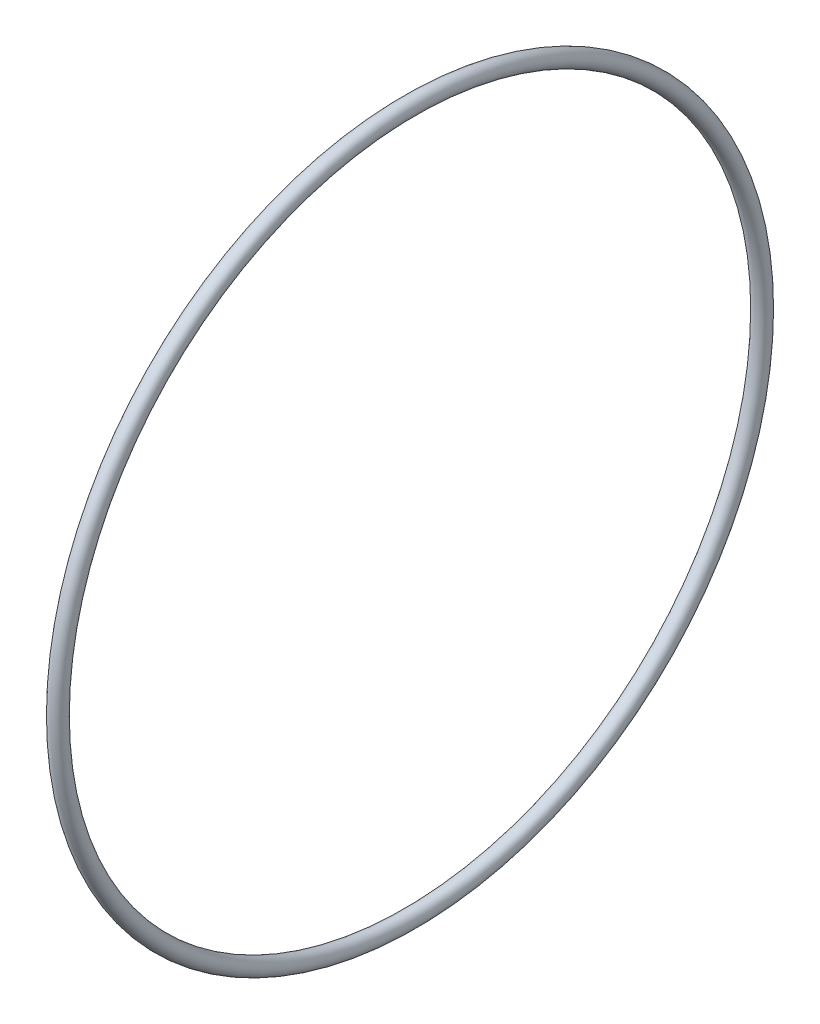
SolidWorks part; units mm, degrees
material "O-Ring (NBR)"
ref_plane "Front Plane" through (0, 0, 0) normal (0, 0, 1) x (1, 0, 0)
ref_plane "Top Plane" through (0, 0, 0) normal (0, 1, 0) x (1, 0, 0)
ref_plane "Right Plane" through (0, 0, 0) normal (1, 0, 0) x (0, 0, -1)
sketch "Sketch3" plane through (0, 0, 0) normal (0, 0, -1) x (-1, 0, 0)
  line L0 (0, 0) -> (5.9943, 0) construction
  circle A0 centre (0, 43.5) radius 1
  dimension "D1" = 85
  dimension "D2" = 2
revolve "Revolve1" add sketch "Sketch3" angle 360 about L0
ref_axis "Axis1" through (-1.1, 0, 0) along (1, 0, 0)
sketch "Sketch1" plane through (0, 0, 0) normal (1, 0, 0) x (0, 0, -1)
  line L0 (-8.772, -54.25) -> (8.772, -54.25)
  line L1 (8.772, 54.25) -> (-8.772, 54.25)
  line L2 (-8.772, -53) -> (8.772, -53) construction
  line L3 (8.772, 53) -> (-8.772, 53) construction
  arc A0 (8.772, -54.25) -> (11.5054, -52.7581) centre (8.772, -51) ccw
  arc A1 (11.5054, 52.7581) -> (8.772, 54.25) centre (8.772, 51) ccw
  arc A2 (-8.772, 54.25) -> (-11.5054, 52.7581) centre (-8.772, 51) ccw
  arc A3 (-11.5054, -52.7581) -> (-8.772, -54.25) centre (-8.772, -51) ccw
  arc A4 (-10.4541, -52.0819) -> (-8.772, -53) centre (-8.772, -51) ccw construction
  arc A5 (8.772, -53) -> (10.4541, -52.0819) centre (8.772, -51) ccw construction
  arc A6 (10.4541, 52.0819) -> (8.772, 53) centre (8.772, 51) ccw construction
  arc A7 (-8.772, 53) -> (-10.4541, 52.0819) centre (-8.772, 51) ccw construction
  spline S0 degree 3 poles (-10.4541, 52.0819) (-16.6114, 42.5088) (-22.7687, 32.9357) (-29.3513, 22.7014) (-29.7886, 22.0215) (-30.4772, 20.9509) (-30.7216, 20.5384) (-31.1954, 19.6712) (-31.4169, 19.2292) (-32.0331, 17.8809) (-32.3797, 16.9524) (-32.9371, 15.0555) (-33.1478, 14.0871) (-33.3589, 12.6197) (-33.4118, 12.1282) (-33.4823, 11.1425) (-33.5, 10.6633) (-33.5, 9.7432) (-33.5, 9.3081) (-33.5, 2.9617) (-33.5, -2.9617) (-33.5, -9.3081) (-33.5, -9.7432) (-33.5, -10.6633) (-33.4823, -11.1425) (-33.4118, -12.1282) (-33.3589, -12.6197) (-33.1478, -14.0871) (-32.9371, -15.0555) (-32.3797, -16.9524) (-32.0331, -17.8809) (-31.4169, -19.2292) (-31.1954, -19.6712) (-30.7216, -20.5384) (-30.4772, -20.9509) (-29.7886, -22.0215) (-29.3513, -22.7014) (-22.7687, -32.9357) (-16.6114, -42.5088) (-10.4541, -52.0819) knots 0.542776 0.542776 0.542776 0.542776 0.662235 0.662235 0.670486 0.670486 0.675984 0.675984 0.681483 0.681483 0.692481 0.692481 0.703479 0.703479 0.708978 0.708978 0.714476 0.714476 0.718917 0.718917 0.781083 0.781083 0.785524 0.785524 0.791022 0.791022 0.796521 0.796521 0.807519 0.807519 0.818517 0.818517 0.824016 0.824016 0.829514 0.829514 0.837765 0.837765 0.957224 0.957224 0.957224 0.957224 construction
  spline S1 degree 3 poles (10.4541, -52.0819) (16.6114, -42.5088) (22.7687, -32.9357) (29.3513, -22.7014) (29.7886, -22.0215) (30.4772, -20.9509) (30.7216, -20.5384) (31.1954, -19.6712) (31.4169, -19.2292) (32.0331, -17.8809) (32.3797, -16.9524) (32.9371, -15.0555) (33.1478, -14.0871) (33.3589, -12.6197) (33.4118, -12.1282) (33.4823, -11.1425) (33.5, -10.6633) (33.5, -9.7432) (33.5, -9.3081) (33.5, -2.9617) (33.5, 2.9617) (33.5, 9.3081) (33.5, 9.7432) (33.5, 10.6633) (33.4823, 11.1425) (33.4118, 12.1282) (33.3589, 12.6197) (33.1478, 14.0871) (32.9371, 15.0555) (32.3797, 16.9524) (32.0331, 17.8809) (31.4169, 19.2292) (31.1954, 19.6712) (30.7216, 20.5384) (30.4772, 20.9509) (29.7886, 22.0215) (29.3513, 22.7014) (22.7687, 32.9357) (16.6114, 42.5088) (10.4541, 52.0819) knots 0.042776 0.042776 0.042776 0.042776 0.162235 0.162235 0.170486 0.170486 0.175984 0.175984 0.181483 0.181483 0.192481 0.192481 0.203479 0.203479 0.208978 0.208978 0.214476 0.214476 0.218917 0.218917 0.281083 0.281083 0.285524 0.285524 0.291022 0.291022 0.296521 0.296521 0.307519 0.307519 0.318517 0.318517 0.324016 0.324016 0.329514 0.329514 0.337765 0.337765 0.457224 0.457224 0.457224 0.457224 construction
  spline S2 degree 3 poles (11.5054, -52.7581) (14.1756, -48.6065) (18.181, -42.3794) (22.854, -35.1136) (25.5242, -30.9628) (27.5271, -27.8466) (29.1952, -25.2599) (30.532, -23.1677) (31.8913, -21.1106) (33.2794, -18.3537) (34.3594, -14.7921) (34.7601, -11.7315) (34.7481, -9.257) (34.7511, -6.7863) (34.7496, -3.7024) (34.7502, 0) (34.7496, 3.7024) (34.7511, 6.7863) (34.7481, 9.257) (34.7601, 11.7315) (34.3594, 14.7921) (33.2794, 18.3537) (31.8913, 21.1106) (30.532, 23.1677) (29.1952, 25.2599) (27.5271, 27.8466) (25.5242, 30.9628) (22.854, 35.1136) (18.181, 42.3794) (14.1756, 48.6065) (11.5054, 52.7581) knots 0.042776 0.042776 0.042776 0.042776 0.094582 0.120485 0.133436 0.146388 0.159339 0.165815 0.172291 0.185242 0.198194 0.211145 0.217621 0.224097 0.237048 0.25 0.262952 0.275903 0.282379 0.288855 0.301806 0.314758 0.327709 0.334185 0.340661 0.353612 0.366564 0.379515 0.405418 0.457224 0.457224 0.457224 0.457224
  spline S3 degree 3 poles (-11.5054, 52.7581) (-14.1756, 48.6065) (-18.181, 42.3794) (-22.854, 35.1136) (-25.5242, 30.9628) (-27.5271, 27.8466) (-29.1952, 25.2599) (-30.532, 23.1677) (-31.8913, 21.1106) (-33.2794, 18.3537) (-34.3594, 14.7921) (-34.7601, 11.7315) (-34.7481, 9.257) (-34.7511, 6.7863) (-34.7496, 3.7024) (-34.7502, 0) (-34.7496, -3.7024) (-34.7511, -6.7863) (-34.7481, -9.257) (-34.7601, -11.7315) (-34.3594, -14.7921) (-33.2794, -18.3537) (-31.8913, -21.1106) (-30.532, -23.1677) (-29.1952, -25.2599) (-27.5271, -27.8466) (-25.5242, -30.9628) (-22.854, -35.1136) (-18.181, -42.3794) (-14.1756, -48.6065) (-11.5054, -52.7581) knots 0.542776 0.542776 0.542776 0.542776 0.594582 0.620485 0.633436 0.646388 0.659339 0.665815 0.672291 0.685242 0.698194 0.711145 0.717621 0.724097 0.737048 0.75 0.762952 0.775903 0.782379 0.788855 0.801806 0.814758 0.827709 0.834185 0.840661 0.853612 0.866564 0.879515 0.905418 0.957224 0.957224 0.957224 0.957224
  point P22 (0, 0)
sketch "Sketch2" plane through (0, 0, 0) normal (0, 0, 1) x (1, 0, 0)
  circle A0 centre (0, 54.25) radius 1
  dimension "D1" = 2
sweep "Sweep1" [suppressed] add profiles "Sketch2" path "Sketch1"
